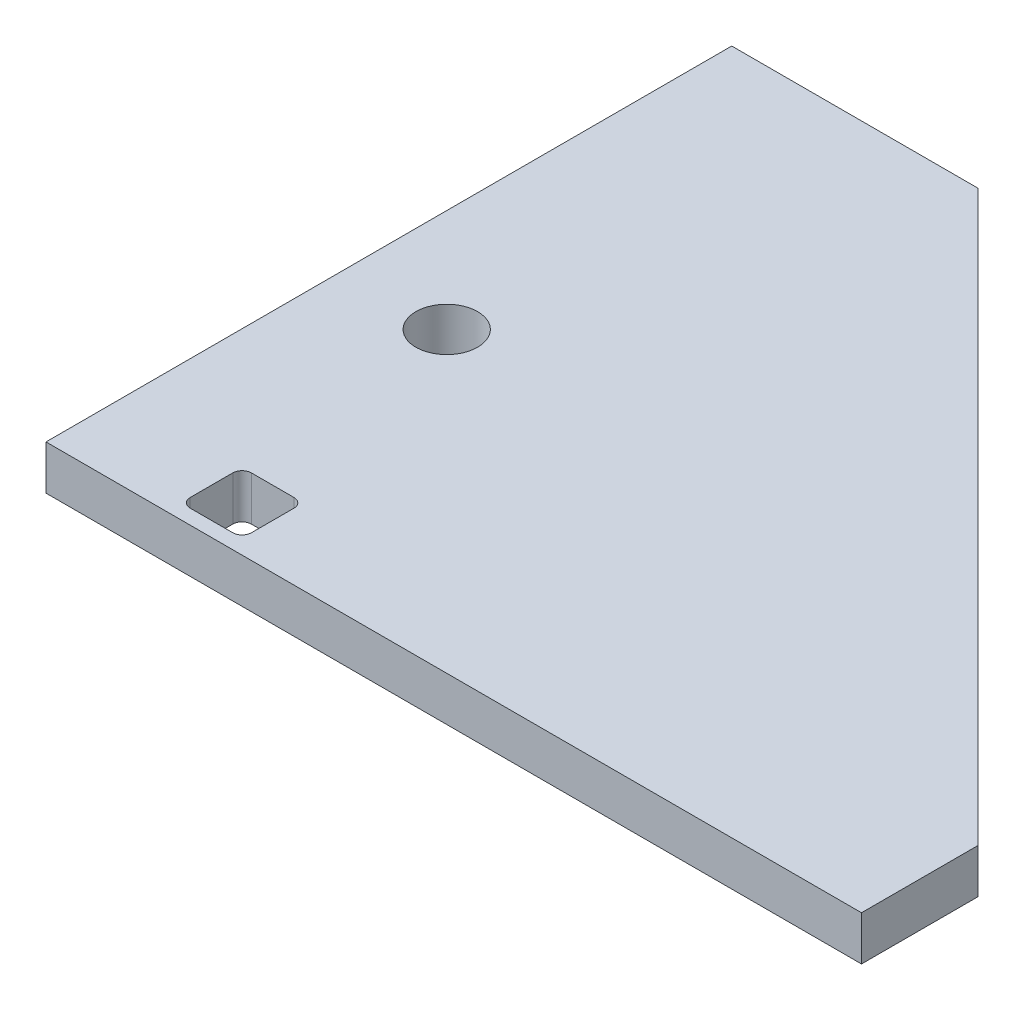
SolidWorks part; units mm, degrees
ref_plane "Front Plane" through (0, 0, 0) normal (0, 0, 1) x (1, 0, 0)
ref_plane "Top Plane" through (0, 0, 0) normal (0, 1, 0) x (1, 0, 0)
ref_plane "Right Plane" through (0, 0, 0) normal (1, 0, 0) x (0, 0, -1)
sketch "Sketch1" plane through (0, 0, 0) normal (0, 1, 0) x (1, 0, 0)
  line L0 (-138.61, 294.305) -> (350, -194.305)
  line L1 (-350, 294.305) -> (-138.61, 294.305)
  line L2 (-350, 294.305) -> (-350, -294.305)
  line L3 (-350, -294.305) -> (350, -294.305)
  line L4 (350, -194.305) -> (350, -294.305)
  line L5 (-350, 294.305) -> (350, -294.305) construction
  point P0 (0, 0)
  dimension "D1" = 588.61
  dimension "D2" = 700
  dimension "D3" = 100
  dimension "D4" = 45
extrude "Boss-Extrude1" add sketch "Sketch1" along normal blind 38.1
sketch "Sketch2" plane through (0, 0, 0) normal (0, -1, 0) x (-1, 0, 0)
  circle A2 centre (261.6329, -38.7118) radius 24.5 construction
  circle A3 centre (261.6329, -38.7118) radius 24.5 construction
  circle A4 centre (261.6329, -38.7118) radius 26.5
  dimension "D1" = 2
extrude "Cut-Extrude1" cut sketch "Sketch2" against normal through all
sketch "Sketch3" plane through (0, 0, 0) normal (0, -1, 0) x (1, 0, 0)
  line L0 (-194.3172, 237.1692) -> (-194.3172, 273.6692)
  line L5 (-202.3172, 281.6692) -> (-238.8172, 281.6692)
  line L6 (-246.8172, 273.6692) -> (-246.8172, 237.1692)
  line L7 (-238.8172, 229.1692) -> (-202.3172, 229.1692)
  line L8 (-196.3172, 237.1692) -> (-196.3172, 273.6692)
  line L9 (-202.3172, 279.6692) -> (-238.8172, 279.6692)
  line L10 (-244.8172, 273.6692) -> (-244.8172, 237.1692)
  line L11 (-238.8172, 231.1692) -> (-202.3172, 231.1692)
  line L12 (-196.3172, 237.1692) -> (-196.3172, 273.6692) construction
  line L13 (-202.3172, 279.6692) -> (-238.8172, 279.6692) construction
  line L14 (-244.8172, 273.6692) -> (-244.8172, 237.1692) construction
  line L15 (-238.8172, 231.1692) -> (-202.3172, 231.1692) construction
  arc A0 (-194.3172, 273.6692) -> (-202.3172, 281.6692) centre (-202.3172, 273.6692) ccw
  arc A1 (-238.8172, 281.6692) -> (-246.8172, 273.6692) centre (-238.8172, 273.6692) ccw
  arc A2 (-246.8172, 237.1692) -> (-238.8172, 229.1692) centre (-238.8172, 237.1692) ccw
  arc A3 (-202.3172, 229.1692) -> (-194.3172, 237.1692) centre (-202.3172, 237.1692) ccw
  arc A4 (-196.3172, 273.6692) -> (-202.3172, 279.6692) centre (-202.3172, 273.6692) ccw
  arc A5 (-238.8172, 279.6692) -> (-244.8172, 273.6692) centre (-238.8172, 273.6692) ccw
  arc A6 (-244.8172, 237.1692) -> (-238.8172, 231.1692) centre (-238.8172, 237.1692) ccw
  arc A7 (-202.3172, 231.1692) -> (-196.3172, 237.1692) centre (-202.3172, 237.1692) ccw
  arc A8 (-196.3172, 273.6692) -> (-202.3172, 279.6692) centre (-202.3172, 273.6692) ccw construction
  arc A9 (-238.8172, 279.6692) -> (-244.8172, 273.6692) centre (-238.8172, 273.6692) ccw construction
  arc A10 (-244.8172, 237.1692) -> (-238.8172, 231.1692) centre (-238.8172, 237.1692) ccw construction
  arc A11 (-202.3172, 231.1692) -> (-196.3172, 237.1692) centre (-202.3172, 237.1692) ccw construction
  dimension "D1" = 0
  dimension "D2" = 2
extrude "Cut-Extrude2" cut sketch "Sketch3" against normal through all
